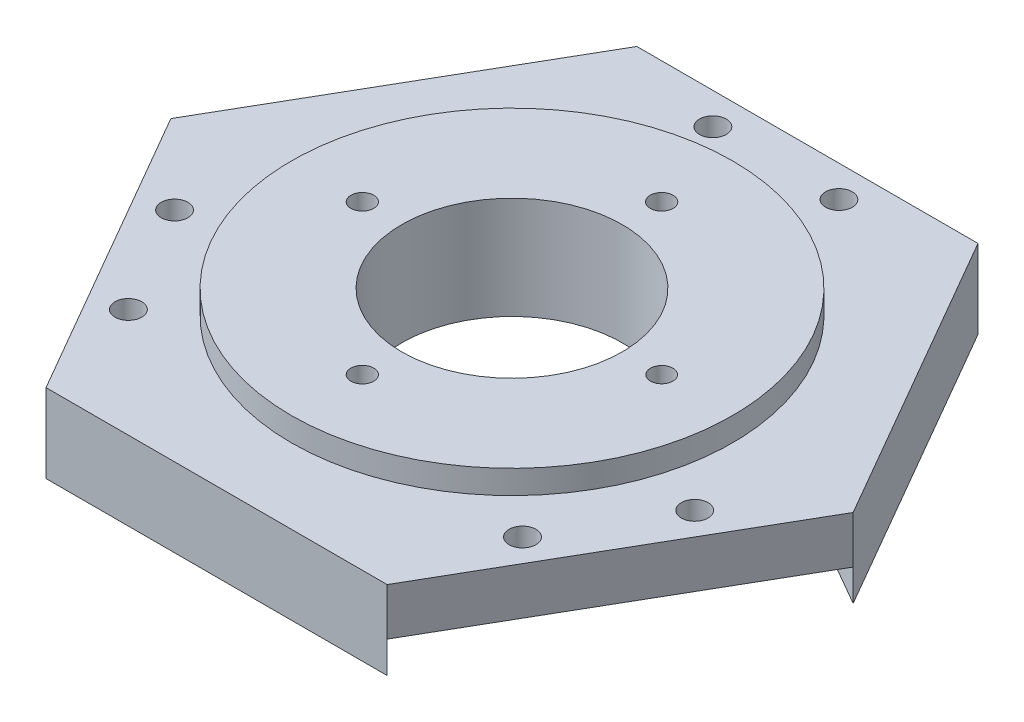
SolidWorks part; units mm, degrees
ref_plane "前视基准面" through (0, 0, 0) normal (0, 0, 1) x (1, 0, 0)
ref_plane "上视基准面" through (0, 0, 0) normal (0, 1, 0) x (1, 0, 0)
ref_plane "右视基准面" through (0, 0, 0) normal (1, 0, 0) x (0, 0, -1)
sketch "草图1" plane through (0, 0, 0) normal (0, 1, 0) x (1, 0, 0)
  line L1 (43.3013, 0) -> (21.6506, 37.5)
  line L2 (21.6506, 37.5) -> (-21.6506, 37.5)
  line L3 (-21.6506, 37.5) -> (-43.3013, 0)
  line L4 (-43.3013, 0) -> (-21.6506, -37.5)
  line L5 (-21.6506, -37.5) -> (21.6506, -37.5)
  line L6 (21.6506, -37.5) -> (43.3013, 0)
  circle A0 centre (0, 0) radius 37.5 construction
  circle A1 centre (0, 0) radius 28 construction
  dimension "D1" = 75
  dimension "D2" = 56
extrude "凸台-拉伸1" add sketch "草图1" along normal blind 10
sketch "草图2" plane through (0, 10, 0) normal (0, 1, 0) x (1, 0, 0)
  line L1 (21.6506, 34.5) -> (-21.6506, 34.5) construction
  line L2 (21.6506, 33) -> (-21.6506, 33)
  line L3 (21.6506, 33) -> (-21.6506, 33) construction
  line L4 (21.6506, 31.5) -> (-21.6506, 31.5) construction
  line L5 (-21.6506, 34.5) -> (-21.6506, 31.5) construction
  line L6 (21.6506, 31.5) -> (21.6506, 34.5) construction
  circle A1 centre (0, 0) radius 19 construction
  circle A2 centre (0, 19) radius 1.45
  circle A3 centre (19, 0) radius 1.45
  circle A4 centre (0, -19) radius 1.45
  circle A5 centre (-19, 0) radius 1.45
  circle A6 centre (0, 0) radius 14
  point P15 (0, 0)
  point P35 (0, 0)
  point P56 (0, 0)
  dimension "D4" = 2.9
  dimension "D5" = 28
  dimension "D6" = 4.5
  dimension "D7" = 1.5
  dimension "D8" = 1.5
  dimension "D3" = 4
extrude "切除-拉伸1" cut sketch "草图2" against normal blind 10 contours A6 | A5 | A2 | A3 | A4 region at (0, 10, 0)
sketch "草图4" plane through (0, 0, 0) normal (0, -1, 0) x (1, 0, 0)
  line L1 (-21.6506, -30.5) -> (21.6506, -30.5)
  line L2 (-21.6506, -37.5) -> (-21.6506, -30.5)
  line L3 (21.6506, -37.5) -> (-21.6506, -37.5)
  line L4 (21.6506, -37.5) -> (-21.6506, -37.5) construction
  line L5 (21.6506, -37.5) -> (21.6506, -30.5)
  line L6 (0, 0) -> (0, -67.6365) construction
  circle A0 centre (-19, 0) radius 3.2
  circle A1 centre (0, -19) radius 3.2
  circle A2 centre (19, 0) radius 3.2
  circle A3 centre (0, 19) radius 3.2
  circle A4 centre (8, -33.5) radius 1.7
  circle A5 centre (-8, -33.5) radius 1.7
  circle M4 centre (0, 19) radius 1.45
  circle M5 centre (19, 0) radius 1.45
  circle M7 centre (-19, 0) radius 1.45
  dimension "D1" = 6.4
  dimension "D2" = 6.4
  dimension "D3" = 6.4
  dimension "D4" = 6.4
  dimension "D6" = 3.4
  dimension "D7" = 8
  dimension "D8" = 3
  dimension "D5" = 7
extrude "切除-拉伸2" cut sketch "草图4" against normal blind 7 contours A0 M7 | A2 M5 | A3 M4 | A1 region at (-22.1095, 0, 0) region at (15.8905, 0, 0) region at (-3.1095, 0, 19)
extrude "切除-拉伸3" cut sketch "草图4<3>" against normal blind 4 contours L1 L5 L3 L2
sketch "草图4<3>" plane through (0, 0, 0) normal (0, -1, 0) x (1, 0, 0) same geometry as "草图4"
extrude "切除-拉伸4" cut sketch "草图4<4>" against normal blind 41 contours A4 | A5
sketch "草图4<4>" plane through (0, 0, 0) normal (0, -1, 0) x (1, 0, 0) same geometry as "草图4"
sketch "草图5" plane through (0, 10, 0) normal (0, 1, 0) x (1, 0, 0)
  circle A0 centre (0, 0) radius 28
  circle A1 centre (0, 0) radius 14
  circle A2 centre (19, 0) radius 1.4269
  circle A3 centre (0, 19) radius 1.45
  circle A4 centre (-19, 0) radius 1.45
  circle A5 centre (0, -19) radius 1.45
extrude "凸台-拉伸2" add sketch "草图5" along normal blind 3
pattern_circular "阵列(圆周)1" count 3 over 360 about axis through (0, 0, 0) along (0, 1, 0) of "切除-拉伸3", "切除-拉伸4"
